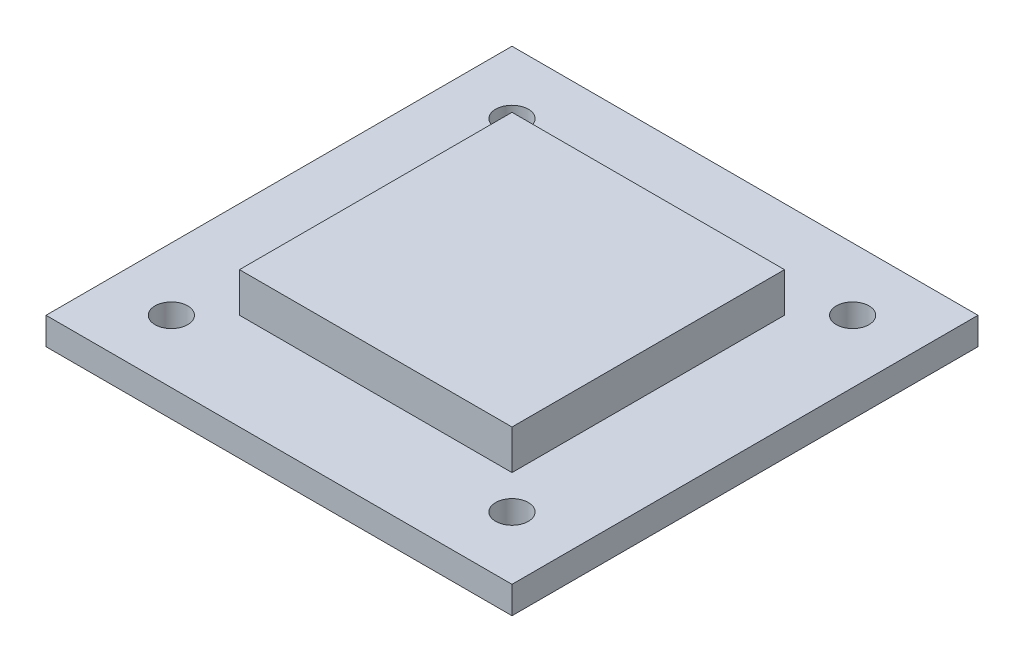
SolidWorks part; units mm, degrees
ref_plane "Front Plane" through (0, 0, 0) normal (0, 0, 1) x (1, 0, 0)
ref_plane "Top Plane" through (0, 0, 0) normal (0, 1, 0) x (1, 0, 0)
ref_plane "Right Plane" through (0, 0, 0) normal (1, 0, 0) x (0, 0, -1)
sketch "Sketch1" plane through (0, 0, 0) normal (0, 1, 0) x (1, 0, 0)
  line L1 (-17.1, 17.1) -> (17.1, 17.1)
  line L2 (-17.1, 17.1) -> (-17.1, -17.1)
  line L3 (-17.1, -17.1) -> (17.1, -17.1)
  line L4 (17.1, 17.1) -> (17.1, -17.1)
  line L5 (-17.1, 17.1) -> (17.1, -17.1) construction
  line L6 (-17.1, -17.1) -> (17.1, 17.1) construction
  point P0 (0, 0)
  dimension "D1" = 34.2
extrude "Boss-Extrude1" add sketch "Sketch1" along normal mid plane 7.8
sketch "Sketch5" plane through (0, 3.9, 0) normal (0, 1, 0) x (1, 0, 0)
  line L1 (12.5, -12.5) -> (-12.5, -12.5) construction
  line L2 (12.5, -12.5) -> (12.5, 12.5) construction
  line L3 (12.5, 12.5) -> (-12.5, 12.5) construction
  line L4 (-12.5, -12.5) -> (-12.5, 12.5) construction
  line L7 (-12.5, -12.5) -> (0, 0) construction
  line L8 (0, 0) -> (-12.5, 12.5) construction
  point P1 (-12.5, 12.5)
  point P2 (12.5, -12.5)
  point P3 (12.5, 12.5)
  point P4 (-12.5, -12.5)
  dimension "D1" = 25
hole_wizard "M2 Clearance Hole1" positions "Sketch5" profile "Sketch8" hole size "M2" standard "ISO" end condition through all
sketch "Sketch8" plane through (-12.5, 3.9, -12.5) normal (1, 0, 0) x (0, 0, 1)
  line L0 (0, 0) -> (0, 7.8)
  line L1 (0, 7.8) -> (1.2, 7.8)
  line L2 (1.2, 7.8) -> (1.2, 0)
  line L5 (1.2, 0) -> (0, 0)
  line L11 (0, -6.35) -> (0, 107.95) construction
  dimension "Thru Hole Dia." = 2.4
  dimension "Thru Hole Depth" = 7.8
sketch "Sketch9" plane through (0, 3.9, 0) normal (0, 1, 0) x (1, 0, 0)
  line L1 (10, -10) -> (-10, -10)
  line L2 (10, -10) -> (10, 10)
  line L3 (10, 10) -> (-10, 10)
  line L4 (-10, -10) -> (-10, 10)
  line L5 (10, -10) -> (-10, 10) construction
  line L6 (10, 10) -> (-10, -10) construction
  line L14 (17.1, -17.1) -> (17.1, 17.1)
  line L15 (17.1, 17.1) -> (-17.1, 17.1)
  line L16 (-17.1, 17.1) -> (-17.1, -17.1)
  line L17 (-17.1, -17.1) -> (17.1, -17.1)
  line L18 (17.1, -17.1) -> (17.1, 17.1)
  line L19 (17.1, 17.1) -> (-17.1, 17.1)
  line L20 (-17.1, 17.1) -> (-17.1, -17.1)
  line L21 (-17.1, -17.1) -> (17.1, -17.1)
  point P0 (0, 0)
  circle M9 centre (-12.5, 12.5) radius 1.2
  circle M10 centre (12.5, -12.5) radius 1.2
  circle M11 centre (12.5, 12.5) radius 1.2
  circle M12 centre (-12.5, -12.5) radius 1.2
  line M13 (17.1, -17.1) -> (17.1, 17.1)
  line M14 (17.1, 17.1) -> (-17.1, 17.1)
  line M15 (-17.1, 17.1) -> (-17.1, -17.1)
  line M16 (-17.1, -17.1) -> (17.1, -17.1)
  dimension "D1" = 20
  dimension "D2" = 0
extrude "Cut-Extrude1" cut sketch "Sketch9" against normal offset from surface (2.9 mm away) 1 contours L1 L4 L3 L2 M16 M13 M14 M15 M10 M12 M11 M9 region at (0, 3.9, 16.6163) up to plane "Top Plane"
mirror "Mirror1" about plane through (0, 0, 0) normal (0, 1, 0) of "Cut-Extrude1"
